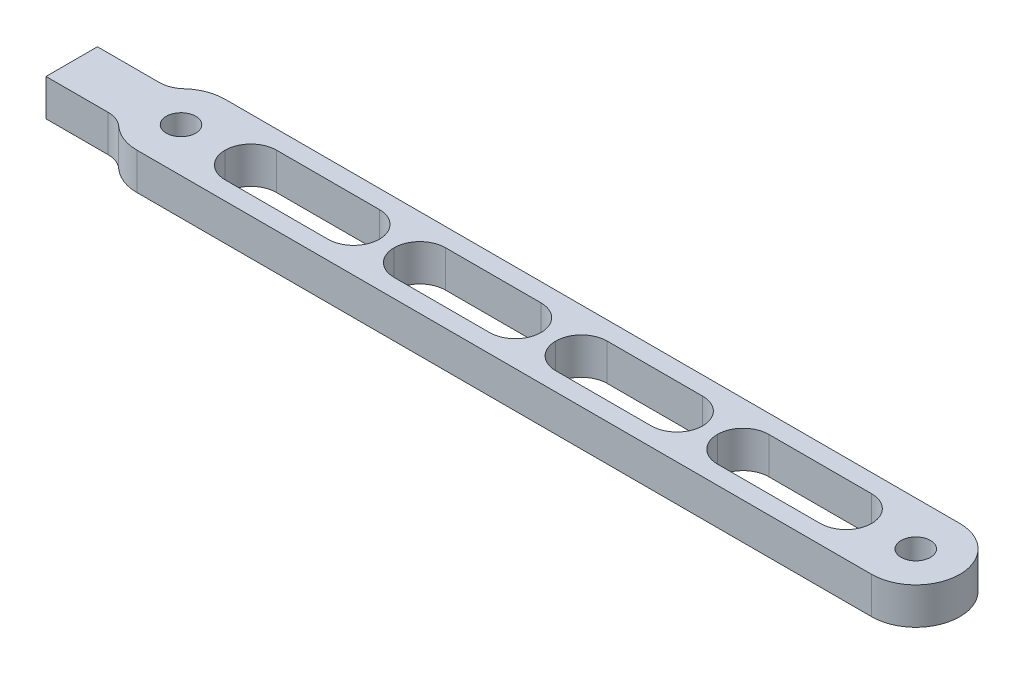
SolidWorks part; units mm, degrees
material "6063-T83"
ref_plane "Front Plane" through (0, 0, 0) normal (0, 0, 1) x (1, 0, 0)
ref_plane "Top Plane" through (0, 0, 0) normal (0, 1, 0) x (1, 0, 0)
ref_plane "Right Plane" through (0, 0, 0) normal (1, 0, 0) x (0, 0, -1)
sketch "Sketch1" plane through (0, 0, 0) normal (0, 1, 0) x (1, 0, 0)
  line L0 (-100, 7) -> (-100, -7) construction
  line L1 (-190.2532, -7) -> (-9.7468, -7) construction
  line L2 (-9.7468, 7) -> (-190.2532, 7) construction
  line L3 (-200, 12) -> (0, 12)
  line L4 (0, -12) -> (-200, -12)
  line L5 (-56, 7) -> (-56, -7) construction
  line L6 (-188, 0) -> (-100, 0) construction
  line L7 (-100, 0) -> (-12, 0) construction
  line L8 (-144, 7) -> (-144, -7) construction
  line L9 (-188, 7) -> (-188, -7)
  line L10 (-146, 7) -> (-146, -7)
  line L11 (-142, 7) -> (-142, -7)
  line L12 (-102, 7) -> (-102, -7)
  line L13 (-98, 7) -> (-98, -7)
  line L14 (-58, 7) -> (-58, -7)
  line L15 (-54, 7) -> (-54, -7)
  line L16 (-12, 7) -> (-12, -7)
  line L17 (-146, 7) -> (-188, 7)
  line L18 (-188, -7) -> (-146, -7)
  line L19 (-142, -7) -> (-102, -7)
  line L20 (-102, 7) -> (-142, 7)
  line L21 (-98, 7) -> (-58, 7)
  line L22 (-98, -7) -> (-58, -7)
  line L23 (-54, -7) -> (-12, -7)
  line L24 (-54, 7) -> (-12, 7)
  line L31 (-200, 0) -> (-200, -44.1421) construction
  line L32 (-200, 0) -> (-229.7468, 0) construction
  line L33 (-229.7468, 7) -> (-209.7468, 7)
  line L34 (-229.7468, 7) -> (-229.7468, -7)
  line L35 (-229.7468, -7) -> (-209.7468, -7)
  circle A0 centre (0, 0) radius 12 construction
  circle A1 centre (-200, 0) radius 12 construction
  circle A2 centre (-200, 0) radius 4
  circle A3 centre (0, 0) radius 4
  arc A5 (0, -12) -> (0, 12) centre (0, 0) ccw
  arc A7 (-200, -12) -> (-209.7468, -7) centre (-200, 0) cw
  arc A9 (-209.7468, 7) -> (-200, 12) centre (-200, 0) cw
  point P22 (-144, 0)
  point P28 (-56, 0)
  point P57 (-229.7468, 0)
  dimension "D2" = 24
  dimension "D3" = 24
  dimension "D4" = 8
  dimension "D5" = 8
  dimension "D1" = 200
  dimension "D6" = 5
  dimension "D7" = 5
  dimension "D8" = 7
  dimension "D9" = 7
  dimension "D10" = 2
  dimension "D11" = 2
  dimension "D12" = 2
  dimension "D13" = 2
  dimension "D14" = 2
  dimension "D15" = 2
  dimension "D16" = 20
extrude "Boss-Extrude1" add sketch "Sketch1" along normal blind 10
fillet "Fillet1" radius 7 18 edges at (-142, 5, -7) (-98, 5, -7) (-54, 5, -7) (-58, 5, -7) (-12, 5, -7) (-102, 5, -7) (-146, 5, -7) (-146, 5, 7) (-102, 5, 7) (-58, 5, 7) (-12, 5, 7) (-54, 5, 7) (-98, 5, 7) (-142, 5, 7) (-188, 5, 7) (-188, 5, -7) (-209.7468, 5, 7) (-209.7468, 5, -7)
